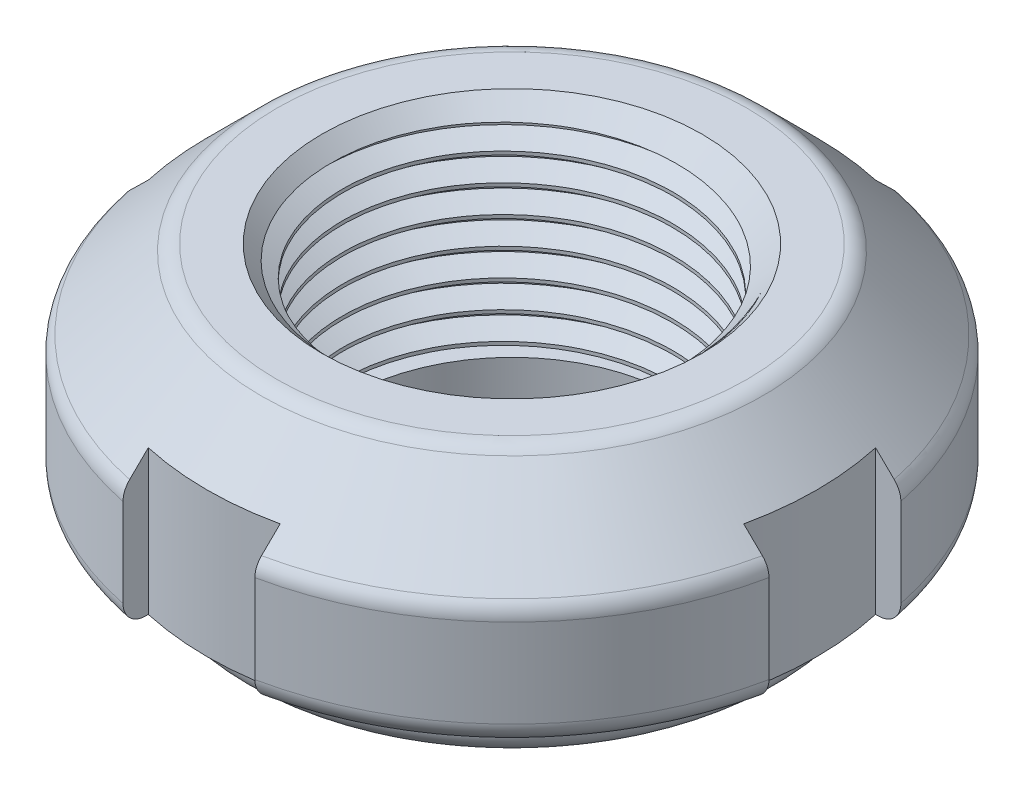
SolidWorks part; units mm, degrees
note: The reader was unsure of these and kept them because the rebuilt part matched: shared geometry of "Sketch13<2>".
ref_plane "Front" through (0, 0, 0) normal (0, 0, 1) x (1, 0, 0)
ref_plane "Top" through (0, 0, 0) normal (0, 1, 0) x (1, 0, 0)
ref_plane "Right" through (0, 0, 0) normal (1, 0, 0) x (0, 0, -1)
sketch "Sketch14" plane through (0, 0, 0) normal (1, 0, 0) x (0, 0, -1)
  line L0 (0, 0) -> (0, 5.6)
  line L1 (0, 0) -> (0, -1.4)
  dimension "Width" = 7
  dimension "D1" = 1.4
sketch "Sketch1" plane through (0, 0, 0) normal (0, 1, 0) x (1, 0, 0)
  circle A1 centre (0, 0) radius 9
  dimension "OD" = 18
extrude "Extrude1" add sketch "Sketch1" along normal up to vertex (5.6 mm away) up to point (0, 5.6, 0)
sketch "Sketch5" plane through (0, 0, 0) normal (1, 0, 0) x (0, 0, -1)
  line L0 (9, 3.2667) -> (6.6667, 5.6)
  line L2 (9, 5.6) -> (-9, 5.6) construction
  line L3 (9, 0) -> (9, 5.6) construction
  line L4 (6.6667, 5.6) -> (9, 5.6)
  line L5 (9, 5.6) -> (9, 3.2667)
  line L15 (0, 0) -> (0, 5.6) construction
  dimension "D1" = 45
  dimension "D2" = 2.3333
revolve "Cut-Revolve3" cut sketch "Sketch5" angle 360 about L15
fillet "Fillet1" radius 0.6048 3 edges at (0, 5.6, -6.6667) (0, 0, 9) (0, 3.2667, -9)
sketch "Sketch6" plane through (0, 5.6, 0) normal (0, 1, 0) x (-1, 0, 0)
  line L0 (1.8, -8.1281) -> (1.8, -9.0465)
  line L1 (1.8, -9.0465) -> (-1.8, -9.0465)
  line L2 (-1.8, -9.0465) -> (-1.8, -8.1281)
  line L3 (0, -9) -> (0, -6.6667) construction
  circle A0 centre (0, 0) radius 9 construction
  circle A1 centre (0, 0) radius 9 construction
  arc A2 (1.8, -8.1281) -> (-1.8, -8.1281) centre (0, 0) cw
  circle A3 centre (0, 0) radius 8.325 construction
  circle A4 centre (0, 0) radius 9 construction
  circle A5 centre (0, 0) radius 6.8438 construction
  point P3 (0, -9)
  point P8 (0, -8.325)
  dimension "D3" = 18
  dimension "D4" = 16.65
  dimension "D1" = 3.6
  dimension "D2" = 0.0465
extrude "Cut-Extrude1" cut sketch "Sketch6" against normal through all
pattern_circular "CirPattern1" count 4 every 90 about axis through (0, 0, 0) along (0, 1, 0) of "Cut-Extrude1"
sketch "Sketch7" plane through (0, 0, 0) normal (0, -1, 0) x (1, 0, 0)
  circle A0 centre (0, 0) radius 7.425
  circle A1 centre (0, 0) radius 8.3952 construction
  dimension "D1" = 14.85
extrude "Extrude2" add sketch "Sketch7" along normal up to vertex (1.4 mm away) draft 4 up to point (0, -1.4, 0)
fillet "Fillet2" radius 0.6048 2 edges at (0, -1.4, -7.3271) (0, 0, 7.425)
sketch "Sketch9" plane through (0, 0, 0) normal (0, 0, 1) x (1, 0, 0)
  line L0 (5, -1.4) -> (5, -2.0563)
  line L1 (5, -2.0563) -> (4.5129, -1.775)
  line L2 (4.5129, -1.775) -> (4.5129, -1.6813)
  line L3 (4.5129, -1.6813) -> (5, -1.4)
  line L4 (5, -1.7281) -> (4.5129, -1.7281) construction
  line L5 (-6.7632, -1.4) -> (6.7632, -1.4) construction
  line L6 (4.7564, -1.5406) -> (4.7564, -1.9156) construction
  line L7 (0, 0) -> (0, -1.4) construction
  dimension "D1" = 60
  dimension "D2" = 0.375
  dimension "D3" = 0.0938
  dimension "Thread Size " = 10
sketch "Sketch10" plane through (0, -1.4, 0) normal (0, -1, 0) x (1, 0, 0)
  circle A0 centre (0, 0) radius 5
  point P3 (5, 0)
extrude "Cut-Extrude2" cut sketch "Sketch10" against normal through all
sketch "Sketch11" plane through (0, -1.4, 0) normal (0, -1, 0) x (1, 0, 0)
  circle A0 centre (0, 0) radius 5
  circle A1 centre (0, 0) radius 5 construction
curve "Helix/Spiral1" pitch 0.75 height 7.75 turns 10.3333 parameters "Width*1.142857143"=7.75, "Thread Pitch "=0.75
chamfer "Chamfer1" distance 0.1875 angle 45 2 edges at (0, -1.4, -5) (0, 5.6, -5)
sweep "Sweep1" add profiles "Sketch9" path "Helix/Spiral1"
sketch "Sketch12" plane through (0, 0, 0) normal (1, 0, 0) x (0, 0, -1)
  line L0 (-6.7632, -1.4) -> (6.7632, -1.4) construction
  line L1 (6.7632, -1.4) -> (0, -1.4) construction
  line L2 (6.7632, -1.4) -> (6.7632, -26.8)
  line L3 (6.7632, -26.8) -> (0, -26.8)
  line L4 (0, -1.4) -> (0, -26.8)
  line L5 (0, 5.6) -> (0, 2.1)
  line L6 (3.3816, -1.4) -> (3.3816, 5.6) construction
  line L7 (4.3301, 5.6) -> (-5, 5.6) construction
  line L8 (3.3816, 2.1) -> (8.8182, 2.1) construction
  line L9 (8.8182, 0.6048) -> (8.8182, 3.0162) construction
  line L10 (0, 5.6) -> (0, 31)
  line L11 (6.7632, 31) -> (0, 31)
  line L12 (6.7632, 5.6) -> (6.7632, 31)
  line L13 (6.7632, 5.6) -> (0, 5.6) construction
  line L14 (1.6875, 2.1) -> (5.1875, 5.6)
  line L15 (0, -1.4) -> (0, 2.1)
  line L16 (1.6875, 2.1) -> (5.1875, -1.4)
  line L17 (5.1875, 5.6) -> (6.7632, 5.6)
  line L18 (5.1875, -1.4) -> (6.7632, -1.4)
  line L19 (6.4162, 5.6) -> (-6.4162, 5.6) construction
  dimension "D1" = 25.4
revolve "Cut-Revolve4" cut sketch "Sketch12" angle 360 about L10
sketch "Sketch13" plane through (0, 0, 0) normal (0, 0, -1) x (0, 1, 0)
  line L1 (-1.4, 4.5129) -> (-0.275, 4.5129)
  line L2 (-1.4, 4.5129) -> (-1.4, 5.6379)
  line L3 (-1.4, 5.6379) -> (-0.275, 5.6379)
  line L4 (-0.275, 4.5129) -> (-0.275, 5.6379)
  line L5 (0, 0) -> (-1.4, 0) construction
  line L6 (-1.775, 4.5129) -> (-1.6813, 4.5129) construction
  line L7 (-1.4, 5) -> (-1.4, -5) construction
  line L8 (-1.4, -4.5129) -> (-0.275, -4.5129) construction
  dimension "D1" = 1.125
  dimension "D2" = 1.125
revolve "Cut-Revolve5" cut sketch "Sketch13" angle 360 about L5
revolve "Revolve1" add sketch "Sketch13<2>" angle 360 about L5
sketch "Sketch13<2>" plane through (0, 0, 0) normal (0, 0, -1) x (0, 1, 0) same geometry as "Sketch13"
equation "\"D1@Sketch6\" = \"OD@Sketch1\"*.2"
equation "\"D2@Sketch6\" = \"OD@Sketch1\" * .0025806452"
equation "\"D1@Sketch7\" = \"OD@Sketch1\" * .825"
equation "\"D1@Fillet2\" = \"D1@Fillet1\""
equation "\"D3@Sketch9\" = \"Thread Pitch @Helix/Spiral1\" * .125"
equation "\"D2@Sketch9\" = \"Thread Pitch @Helix/Spiral1\" * .5"
equation "\"D1@Chamfer1\" = \"Thread Pitch @Helix/Spiral1\" * .25"
equation "\"D1@Sketch13\" = \"Thread Pitch @Helix/Spiral1\" * 1.5"
equation "\"D2@Sketch13\" = \"Thread Pitch @Helix/Spiral1\" * 1.5"
equation "\"D1@Sketch14\" = \"Width@Sketch14\"*.2"
equation "\"Width*1.142857143@Helix/Spiral1\" = \"Width@Sketch14\"+\"Thread Pitch @Helix/Spiral1\""
equation "\"D2@Sketch5\" = \"Width@Sketch14\"/3"
equation "\"D4@Sketch6\" = \"D3@Sketch6\"*.925"
